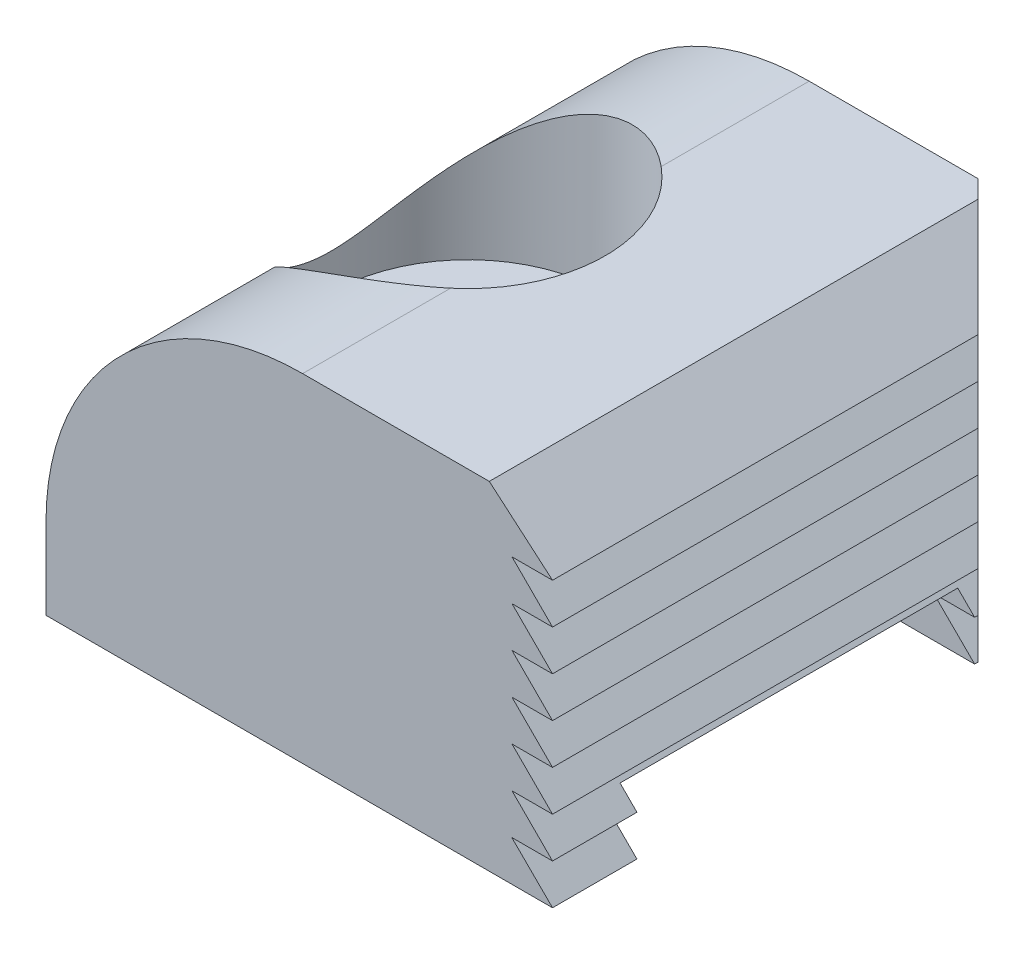
SolidWorks part; units mm, degrees
ref_plane "Alzado" through (0, 0, 0) normal (0, 0, 1) x (1, 0, 0)
ref_plane "Planta" through (0, 0, 0) normal (0, 1, 0) x (1, 0, 0)
ref_plane "Vista lateral" through (0, 0, 0) normal (1, 0, 0) x (0, 0, -1)
sketch "Croquis1" plane through (0, 0, 0) normal (1, 0, 0) x (0, 0, -1)
  line L1 (-9.525, 6.3151) -> (9.525, 6.3151)
  line L2 (-9.525, 6.3151) -> (-9.525, -6.3849)
  line L3 (-9.525, -6.3849) -> (9.525, -6.3849)
  line L4 (9.525, 6.3151) -> (9.525, -6.3849)
  line L5 (0, -6.3849) -> (0, 6.3151) construction
  line L6 (-9.525, -0.0349) -> (9.525, -0.0349) construction
  point P232 (0, -0.0349)
  dimension "D1" = 19.05
  dimension "D2" = 12.7
extrude "Saliente-Extruir1" add sketch "Croquis1" along normal blind 19.05 contours L1 L4 L3 L2
sketch "Croquis2" plane through (0, 0, 0) normal (-1, 0, 0) x (0, 0, 1)
  line L1 (-6.35, -4.2259) -> (6.35, -4.2259)
  line L2 (-6.35, -4.2259) -> (-6.35, -6.3849)
  line L3 (-6.35, -6.3849) -> (6.35, -6.3849)
  line L4 (6.35, -4.2259) -> (6.35, -6.3849)
  line L5 (0, -6.3849) -> (0, -4.2259) construction
  line L6 (-6.35, -5.3054) -> (6.35, -5.3054) construction
  point P212 (0, -5.3054)
  dimension "D1" = 12.7
  dimension "D2" = 2.159
extrude "Cortar-Extruir1" cut sketch "Croquis2" against normal through all
chamfer "Chaflán1" distance 3.048 angle 45 1 edges at (19.05, -0.0349, -9.525)
sketch "Croquis9" plane through (0, 6.3151, 0) normal (0, 1, 0) x (1, 0, 0)
  circle A0 centre (6.35, 0) radius 5.1562
  dimension "D1" = 6.35
  dimension "D3" = 10.3124
  dimension "D2" = 9.525
extrude "Cortar-Extruir4" cut sketch "Croquis9" against normal blind 6.35
sketch "Croquis17" plane through (0, 6.3151, 0) normal (0, 1, 0) x (1, 0, 0)
  circle A0 centre (6.35, 0) radius 3.2639
  dimension "D1" = 6.35
  dimension "D3" = 6.5278
  dimension "D2" = 9.525
extrude "Cortar-Extruir5" cut sketch "Croquis17" against normal through all
fillet "Redondeo1" radius 9.652 1 edges at (0, 6.3151, 0) type face fillet first side face at (0, -2.6702, 0) second side face at (6.35, 6.3151, 5.1562)
sketch "Croquis20" plane through (0, 0, 9.525) normal (0, 0, 1) x (1, 0, 0)
  line L0 (19.05, -6.3849) -> (19.05, -4.8609)
  line L1 (19.05, 6.3151) -> (19.05, -6.3849) construction
  line L2 (19.05, -4.8609) -> (17.5173, -4.8609)
  line L3 (17.5173, -4.8609) -> (19.05, -6.3849)
  dimension "D1" = 1.524
extrude "Cortar-Extruir6" cut sketch "Croquis20" against normal through all
sketch "Croquis21" plane through (0, 0, 9.525) normal (0, 0, 1) x (1, 0, 0)
  line L0 (19.05, -4.8609) -> (19.05, -3.3369)
  line L1 (19.05, 6.3151) -> (19.05, -4.8609) construction
  line L2 (19.05, -3.3369) -> (17.526, -3.3369)
  line L3 (17.526, -3.3369) -> (19.05, -4.8609)
extrude "Cortar-Extruir7" cut sketch "Croquis21" against normal through all
sketch "Croquis22" plane through (0, 0, 9.525) normal (0, 0, 1) x (1, 0, 0)
  line L0 (19.05, -3.3369) -> (19.05, -1.8129)
  line L1 (19.05, 6.3151) -> (19.05, -3.3369) construction
  line L2 (19.05, -1.8129) -> (17.526, -1.8129)
  line L3 (17.526, -1.8129) -> (19.05, -3.3369)
extrude "Cortar-Extruir8" cut sketch "Croquis22" against normal through all
sketch "Croquis23" plane through (0, 0, 9.525) normal (0, 0, 1) x (1, 0, 0)
  line L0 (19.05, -1.8129) -> (19.05, -0.2889)
  line L1 (19.05, 6.3151) -> (19.05, -1.8129) construction
  line L2 (19.05, -0.2889) -> (17.526, -0.2889)
  line L3 (17.526, -0.2889) -> (19.05, -1.8129)
extrude "Cortar-Extruir9" cut sketch "Croquis23" against normal through all
sketch "Croquis24" plane through (0, 0, 9.525) normal (0, 0, 1) x (1, 0, 0)
  line L0 (19.05, -0.2889) -> (19.05, 1.2351)
  line L1 (19.05, 6.3151) -> (19.05, -0.2889) construction
  line L2 (19.05, 1.2351) -> (17.526, 1.2351)
  line L3 (17.526, 1.2351) -> (19.05, -0.2889)
extrude "Cortar-Extruir10" cut sketch "Croquis24" against normal through all
sketch "Croquis25" plane through (0, 0, 9.525) normal (0, 0, 1) x (1, 0, 0)
  line L0 (19.05, 1.2351) -> (19.05, 2.7591)
  line L1 (19.05, 6.3151) -> (19.05, 1.2351) construction
  line L2 (19.05, 2.7591) -> (17.526, 2.7591)
  line L3 (17.526, 2.7591) -> (19.05, 1.2351)
extrude "Cortar-Extruir11" cut sketch "Croquis25" against normal through all
sketch "Croquis26" plane through (0, 0, 9.525) normal (0, 0, 1) x (1, 0, 0)
  line L0 (19.05, 2.7591) -> (19.05, 4.2831)
  line L1 (19.05, 6.3151) -> (19.05, 2.7591) construction
  line L2 (19.05, 4.2831) -> (17.526, 4.2831)
  line L3 (17.526, 4.2831) -> (19.05, 2.7591)
extrude "Cortar-Extruir12" cut sketch "Croquis26" against normal through all
sketch "Croquis27" plane through (0, 0, 9.525) normal (0, 0, 1) x (1, 0, 0)
  line L0 (19.05, 4.2831) -> (16.6726, 6.3151)
  line L1 (19.05, 6.3151) -> (9.652, 6.3151) construction
  line L2 (16.6726, 6.3151) -> (19.05, 6.3151)
  line L3 (19.05, 6.3151) -> (19.05, 4.2831) construction
  line L4 (19.05, 6.3151) -> (19.05, 4.2831)
extrude "Cortar-Extruir13" cut sketch "Croquis27" against normal through all
